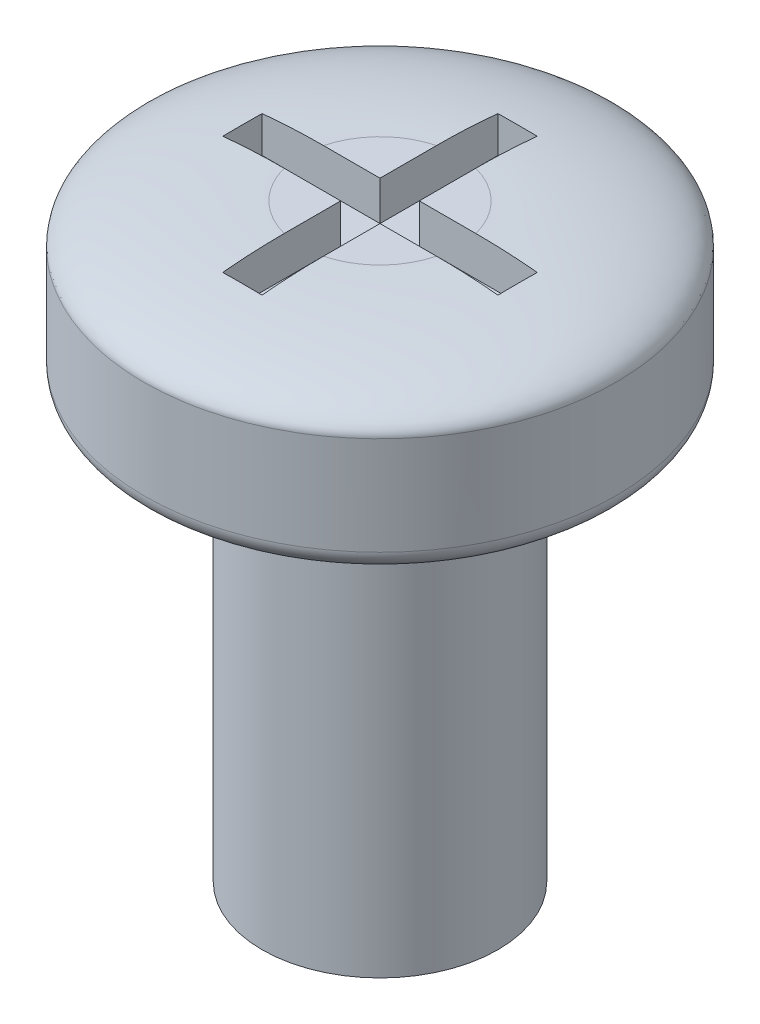
SolidWorks part; units mm, degrees
ref_plane "Front Plane" through (0, 0, 0) normal (0, 0, 1) x (1, 0, 0)
ref_plane "Top Plane" through (0, 0, 0) normal (0, 1, 0) x (1, 0, 0)
ref_plane "Right Plane" through (0, 0, 0) normal (1, 0, 0) x (0, 0, -1)
sketch "Sketch1" plane through (0, 0, 0) normal (0, 1, 0) x (1, 0, 0)
  circle A0 centre (0, 0) radius 3
extrude "Boss-Extrude1" add sketch "Sketch1" along normal blind 2
sketch "Sketch2" plane through (0, 0, 0) normal (0, -1, 0) x (1, 0, 0)
  circle A0 centre (0, 0) radius 1.5
extrude "Boss-Extrude2" add sketch "Sketch2" along normal blind 5.5
fillet "Fillet2" radius 0.5 1 edges at (0, 2, 3) second distance 2 first distance on face at (0, 2, 3)
sketch "Sketch3" plane through (0, 2, 0) normal (0, 1, 0) x (1, 0, 0)
  line L1 (-1.75, -0.25) -> (1.75, -0.25)
  line L2 (-1.75, -0.25) -> (-1.75, 0.25)
  line L3 (-1.75, 0.25) -> (1.75, 0.25)
  line L4 (1.75, -0.25) -> (1.75, 0.25)
  line L5 (-1.75, -0.25) -> (1.75, 0.25) construction
  line L6 (-1.75, 0.25) -> (1.75, -0.25) construction
  line L7 (-0.25, -1.75) -> (0.25, -1.75)
  line L8 (-0.25, -1.75) -> (-0.25, 1.75)
  line L9 (-0.25, 1.75) -> (0.25, 1.75)
  line L10 (0.25, -1.75) -> (0.25, 1.75)
  line L11 (-0.25, -1.75) -> (0.25, 1.75) construction
  line L12 (-0.25, 1.75) -> (0.25, -1.75) construction
  point P0 (0, 0)
  point P6 (0, 0)
extrude "Cut-Extrude1" cut sketch "Sketch3" against normal blind 0.5 contours L3 L10 L8 | L10 L9 L8 | L10 L1 L3 | L1 L4 L3 | L10 L1 L8 | L7 L10 L8 | L1 L8 L3 | L3 L2 L1 | L1 L10 L3 L8 region at (-1, 2, 0) region at (0, 2, 0) region at (0, 2, 1) region at (1, 2, 0) region at (0, 2, -1)
fillet "Fillet3" radius 0.25 1 edges at (0, 0, 3)
